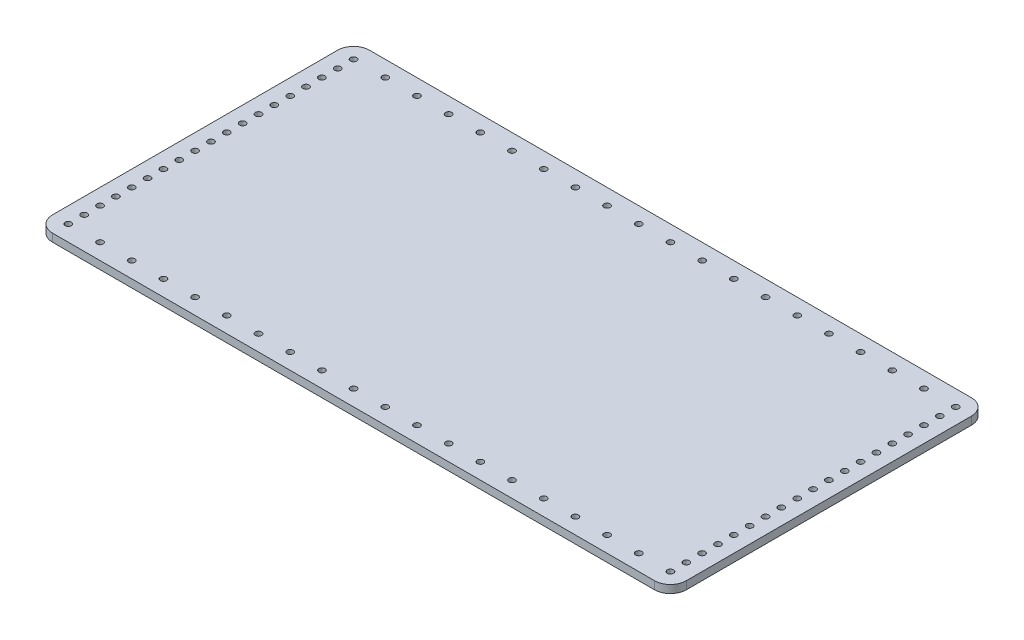
SolidWorks part; units mm, degrees
material "PC High Viscosity"
ref_plane "Front Plane" through (0, 0, 0) normal (0, 0, 1) x (1, 0, 0)
ref_plane "Top Plane" through (0, 0, 0) normal (0, 1, 0) x (1, 0, 0)
ref_plane "Right Plane" through (0, 0, 0) normal (1, 0, 0) x (0, 0, -1)
sketch "Sketch1" plane through (0, 0, 0) normal (0, 1, 0) x (1, 0, 0)
  line L1 (0, 0) -> (508, 0)
  line L2 (0, 0) -> (0, 254)
  line L3 (0, 254) -> (508, 254)
  line L4 (508, 0) -> (508, 254)
  dimension "D1" = 508
  dimension "D2" = 254
extrude "Boss-Extrude1" add sketch "Sketch1" along normal blind 6.35
sketch "Sketch3" plane through (0, 6.35, 0) normal (0, 1, 0) x (1, 0, 0)
  line L0 (508, 254) -> (0, 254) construction
  line L1 (0, 254) -> (0, 0) construction
  line L2 (12.7, 241.3) -> (38.1, 241.3) construction
  line L3 (12.7, 241.3) -> (12.7, 228.6) construction
  line L4 (12.7, 12.7) -> (38.1, 12.7) construction
  line L5 (12.7, 215.9) -> (12.7, 190.5) construction
  line L6 (495.3, 241.3) -> (495.3, 228.6) construction
  circle A0 centre (12.7, 241.3) radius 2.4892
  circle A1 centre (38.1, 241.3) radius 2.4892
  circle A2 centre (63.5, 241.3) radius 2.4892
  circle A3 centre (88.9, 241.3) radius 2.4892
  circle A4 centre (114.3, 241.3) radius 2.4892
  circle A5 centre (139.7, 241.3) radius 2.4892
  circle A6 centre (165.1, 241.3) radius 2.4892
  circle A7 centre (190.5, 241.3) radius 2.4892
  circle A8 centre (215.9, 241.3) radius 2.4892
  circle A9 centre (241.3, 241.3) radius 2.4892
  circle A10 centre (266.7, 241.3) radius 2.4892
  circle A11 centre (292.1, 241.3) radius 2.4892
  circle A12 centre (317.5, 241.3) radius 2.4892
  circle A13 centre (342.9, 241.3) radius 2.4892
  circle A14 centre (368.3, 241.3) radius 2.4892
  circle A15 centre (393.7, 241.3) radius 2.4892
  circle A16 centre (419.1, 241.3) radius 2.4892
  circle A17 centre (444.5, 241.3) radius 2.4892
  circle A18 centre (469.9, 241.3) radius 2.4892
  circle A19 centre (495.3, 241.3) radius 2.4892
  circle A23 centre (12.7, 228.6) radius 2.4892
  circle A24 centre (12.7, 215.9) radius 2.4892
  circle A25 centre (12.7, 203.2) radius 2.4892
  circle A26 centre (12.7, 190.5) radius 2.4892
  circle A27 centre (12.7, 177.8) radius 2.4892
  circle A28 centre (12.7, 165.1) radius 2.4892
  circle A29 centre (12.7, 152.4) radius 2.4892
  circle A30 centre (12.7, 139.7) radius 2.4892
  circle A31 centre (12.7, 127) radius 2.4892
  circle A32 centre (12.7, 114.3) radius 2.4892
  circle A33 centre (12.7, 101.6) radius 2.4892
  circle A56 centre (12.7, 215.9) radius 2.4892
  circle A57 centre (12.7, 190.5) radius 2.4892
  circle A58 centre (12.7, 165.1) radius 2.4892
  circle A59 centre (12.7, 139.7) radius 2.4892
  circle A60 centre (12.7, 114.3) radius 2.4892
  circle A61 centre (12.7, 88.9) radius 2.4892
  circle A62 centre (12.7, 63.5) radius 2.4892
  circle A63 centre (12.7, 38.1) radius 2.4892
  circle A64 centre (12.7, 12.7) radius 2.4892
  circle A65 centre (12.7, 88.9) radius 2.4892
  circle A66 centre (12.7, 76.2) radius 2.4892
  circle A67 centre (12.7, 63.5) radius 2.4892
  circle A68 centre (12.7, 50.8) radius 2.4892
  circle A69 centre (12.7, 38.1) radius 2.4892
  circle A70 centre (12.7, 25.4) radius 2.4892
  circle A71 centre (12.7, 12.7) radius 2.4892
  circle A72 centre (38.1, 12.7) radius 2.4892
  circle A73 centre (63.5, 12.7) radius 2.4892
  circle A74 centre (88.9, 12.7) radius 2.4892
  circle A75 centre (114.3, 12.7) radius 2.4892
  circle A76 centre (139.7, 12.7) radius 2.4892
  circle A77 centre (165.1, 12.7) radius 2.4892
  circle A78 centre (190.5, 12.7) radius 2.4892
  circle A79 centre (215.9, 12.7) radius 2.4892
  circle A80 centre (241.3, 12.7) radius 2.4892
  circle A81 centre (266.7, 12.7) radius 2.4892
  circle A82 centre (292.1, 12.7) radius 2.4892
  circle A83 centre (317.5, 12.7) radius 2.4892
  circle A84 centre (342.9, 12.7) radius 2.4892
  circle A85 centre (368.3, 12.7) radius 2.4892
  circle A86 centre (393.7, 12.7) radius 2.4892
  circle A87 centre (419.1, 12.7) radius 2.4892
  circle A88 centre (444.5, 12.7) radius 2.4892
  circle A89 centre (469.9, 12.7) radius 2.4892
  circle A90 centre (495.3, 12.7) radius 2.4892
  circle A91 centre (495.3, 228.6) radius 2.4892
  circle A92 centre (495.3, 215.9) radius 2.4892
  circle A93 centre (495.3, 203.2) radius 2.4892
  circle A94 centre (495.3, 190.5) radius 2.4892
  circle A95 centre (495.3, 177.8) radius 2.4892
  circle A96 centre (495.3, 165.1) radius 2.4892
  circle A97 centre (495.3, 152.4) radius 2.4892
  circle A98 centre (495.3, 139.7) radius 2.4892
  circle A99 centre (495.3, 127) radius 2.4892
  circle A100 centre (495.3, 114.3) radius 2.4892
  circle A101 centre (495.3, 101.6) radius 2.4892
  circle A102 centre (495.3, 88.9) radius 2.4892
  circle A103 centre (495.3, 76.2) radius 2.4892
  circle A104 centre (495.3, 63.5) radius 2.4892
  circle A105 centre (495.3, 50.8) radius 2.4892
  circle A106 centre (495.3, 38.1) radius 2.4892
  circle A107 centre (495.3, 25.4) radius 2.4892
  dimension "D1" = 12.7
  dimension "D2" = 4.9784
  dimension "D3" = 12.7
  dimension "D10" = 12.7
  dimension "D5" = 25.4
  dimension "D7" = 12.7
  dimension "D9" = 25.4
  dimension "D12" = 25.4
  dimension "D14" = 12.7
  dimension "D4" = 20
  dimension "D6" = 19
  dimension "D11" = 9
  dimension "D8" = 20
  dimension "D13" = 18
fillet "Fillet1" radius 12.7 4 edges at (508, 3.175, -254) (508, 3.175, 0) (0, 3.175, 0) (0, 3.175, -254)
extrude "Cut-Extrude2" cut sketch "Sketch3" against normal through all contours A25 | A24 | A23 | A0 | A1 | A2 | A3 | A4 | A64 | A70 | A63 | A68 | A62 | A72 | A73 | A74 | A33 | A32 | A31 | A30 | A28 | A29 | A27 | A26 | A61 | A66 | A90 | A89 | A88 | A87 | A86 | A85 | A84 | A83 | A82 | A81 | A80 | A79 | A75 | A76 | A77 | A78 | A5 | A6 | A7 | A8 | A9 | A10 | A11 | A12 | A13 | A14 | A15 | A16 | A17 | A18 | A19 | A107 | A106 | A105 | A101 | A102 | A103 | A104 | A100 | A99 | A98 | A97 | A96 | A95 | A94 | A93 | A91 | A92 region at (12.7, 6.35, -241.3) region at (38.1, 6.35, -241.3) region at (63.5, 6.35, -241.3) region at (88.9, 6.35, -241.3) region at (114.3, 6.35, -241.3) region at (139.7, 6.35, -241.3) region at (165.1, 6.35, -241.3) region at (190.5, 6.35, -241.3) region at (215.9, 6.35, -241.3) region at (241.3, 6.35, -241.3) region at (266.7, 6.35, -241.3) region at (292.1, 6.35, -241.3) region at (317.5, 6.35, -241.3) region at (342.9, 6.35, -241.3) region at (368.3, 6.35, -241.3) region at (393.7, 6.35, -241.3) region at (419.1, 6.35, -241.3) region at (444.5, 6.35, -241.3) region at (469.9, 6.35, -241.3) region at (495.3, 6.35, -241.3) region at (12.7, 6.35, -228.6) region at (12.7, 6.35, -215.9) region at (12.7, 6.35, -203.2) region at (12.7, 6.35, -190.5) region at (12.7, 6.35, -177.8) region at (12.7, 6.35, -165.1) region at (12.7, 6.35, -152.4) region at (12.7, 6.35, -139.7) region at (12.7, 6.35, -127) region at (12.7, 6.35, -114.3) region at (12.7, 6.35, -101.6) region at (12.7, 6.35, -88.9) region at (12.7, 6.35, -63.5) region at (12.7, 6.35, -38.1) region at (12.7, 6.35, -12.7) region at (12.7, 6.35, -76.2) region at (12.7, 6.35, -50.8) region at (12.7, 6.35, -25.4) region at (38.1, 6.35, -12.7) region at (63.5, 6.35, -12.7) region at (88.9, 6.35, -12.7) region at (114.3, 6.35, -12.7) region at (139.7, 6.35, -12.7) region at (165.1, 6.35, -12.7) region at (190.5, 6.35, -12.7) region at (215.9, 6.35, -12.7) region at (241.3, 6.35, -12.7) region at (266.7, 6.35, -12.7) region at (292.1, 6.35, -12.7) region at (317.5, 6.35, -12.7) region at (342.9, 6.35, -12.7) region at (368.3, 6.35, -12.7) region at (393.7, 6.35, -12.7) region at (419.1, 6.35, -12.7) region at (444.5, 6.35, -12.7) region at (469.9, 6.35, -12.7) region at (495.3, 6.35, -12.7) region at (495.3, 6.35, -228.6) region at (495.3, 6.35, -203.2) region at (495.3, 6.35, -190.5)
